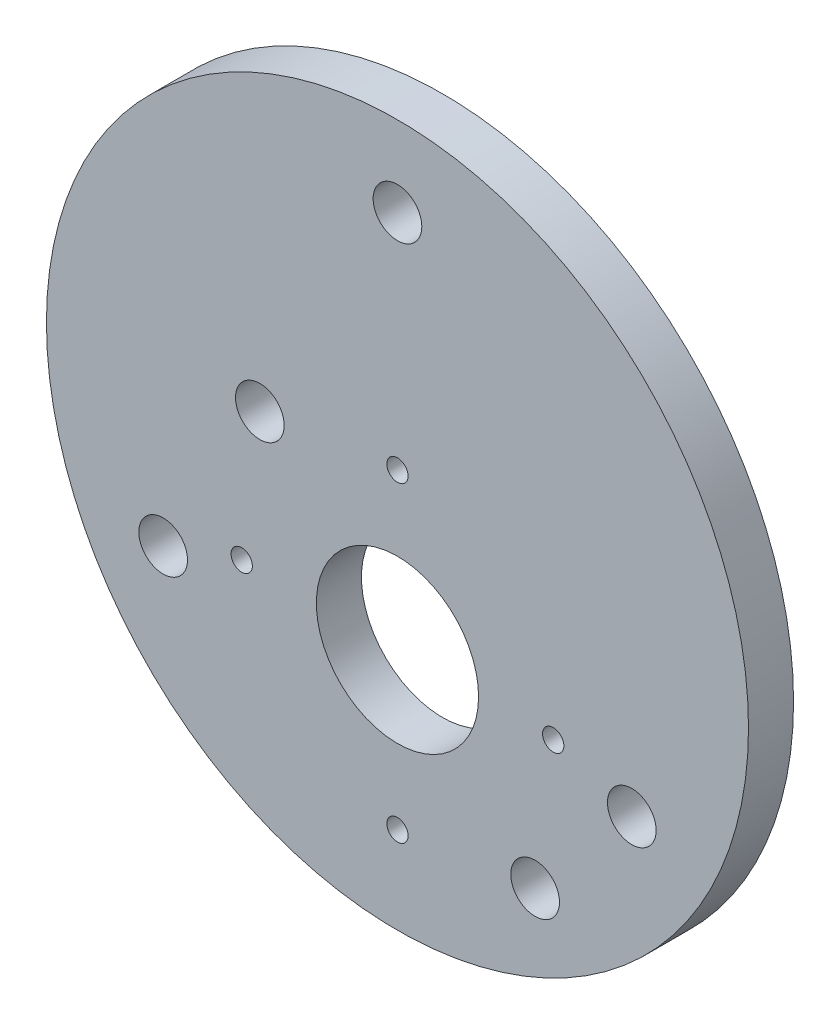
SolidWorks part; units mm, degrees
ref_plane "Front Plane" through (0, 0, 0) normal (0, 0, 1) x (1, 0, 0)
ref_plane "Top Plane" through (0, 0, 0) normal (0, 1, 0) x (1, 0, 0)
ref_plane "Right Plane" through (0, 0, 0) normal (1, 0, 0) x (0, 0, -1)
sketch "Sketch1" plane through (0, 0, 0) normal (0, 0, 1) x (1, 0, 0)
  circle A0 centre (0, 0) radius 49.4665
  dimension "D1" = 98.933
extrude "Boss-Extrude1" add sketch "Sketch1" along normal blind 6.35
sketch "Sketch2" plane through (0, 0, 6.35) normal (0, 0, 1) x (1, 0, 0)
  line L0 (0, -37.1877) -> (0, 6.7077) construction
  line L1 (-21.9477, -15.24) -> (0, 6.7077)
  line L2 (-21.9477, -15.24) -> (0, -37.1877)
  line L3 (0, -37.1877) -> (21.9477, -15.24)
  line L4 (0, 6.7077) -> (21.9477, -15.24)
  line L5 (0, -15.24) -> (12.0918, -15.24) construction
  point P4 (0, -15.24)
  dimension "D1" = 31.0388
  dimension "D2" = 31.0388
  dimension "D3" = 15.24
  dimension "D4" = 90
hole_wizard "M3 Screw Hole - Ø3.0mm Dowel Hole" positions "Sketch3" profile "Sketch4" hole size "Ø3.0" standard "ANSI Metric" end condition through all
sketch "Sketch3" plane through (0, 0, 6.35) normal (0, 0, 1) x (1, 0, 0)
  point P0 (0, 6.7077)
  point P3 (-21.9477, -15.24)
  point P6 (0, -37.1877)
  point P9 (21.9477, -15.24)
sketch "Sketch4" plane through (0, 6.7077, 6.35) normal (1, 0, 0) x (0, -1, 0)
  line L0 (0, 0) -> (0, 6.35)
  line L1 (0, 6.35) -> (1.5, 6.35)
  line L2 (1.5, 6.35) -> (1.5, 0)
  line L5 (1.5, 0) -> (0, 0)
  line L11 (0, -6.35) -> (0, 107.95) construction
  dimension "Thru Hole Dia." = 3
  dimension "Thru Hole Depth" = 6.35
sketch "Sketch5" plane through (0, 0, 6.35) normal (0, 0, 1) x (1, 0, 0)
  line L0 (0, -37.1877) -> (0, 6.7077) construction
  line L1 (-29.9941, -15.24) -> (0, 14.7541)
  line L2 (-29.9941, -15.24) -> (0, -45.2341)
  line L3 (0, -45.2341) -> (29.9941, -15.24)
  line L4 (0, 14.7541) -> (29.9941, -15.24)
  line L5 (-29.9941, -15.24) -> (29.9941, -15.24) construction
  line L6 (0, -45.2341) -> (0, 14.7541) construction
  line L7 (-19.3974, 4.1574) -> (0, -15.24) construction
  line L8 (0, -15.24) -> (32.8719, -15.24) construction
  line L9 (0, -15.24) -> (19.3974, -34.6374) construction
  circle A0 centre (19.3974, -34.6374) radius 3.429
  circle A1 centre (-19.3974, 4.1574) radius 3.429
  point P0 (0, -15.24)
  point P7 (0, -15.24)
  dimension "D3" = 6.858
  dimension "D5" = 6.858
  dimension "D1" = 42.418
  dimension "D4" = 42.418
  dimension "D6" = 27.432
  dimension "D7" = 135
extrude "Cut-Extrude1" cut sketch "Sketch5" against normal through all contours A0 | A1 region at (19.3974, -34.6374, 6.35)
sketch "Sketch6" plane through (0, 0, 6.35) normal (0, 0, 1) x (1, 0, 0)
  line L0 (0, 38.1282) -> (-33.02, -19.0641) construction
  line L1 (-33.02, -19.0641) -> (33.02, -19.0641) construction
  line L2 (33.02, -19.0641) -> (0, 38.1282) construction
  line L3 (-33.02, -19.0641) -> (0, 0) construction
  line L4 (0, 0) -> (33.02, -19.0641) construction
  line L5 (0, 0) -> (0, 38.1282) construction
  circle A0 centre (0, 38.1282) radius 3.429
  circle A1 centre (-33.02, -19.0641) radius 3.429
  circle A2 centre (33.02, -19.0641) radius 3.429
  dimension "D1" = 6.858
  dimension "D2" = 66.04
  dimension "D3" = 60
  dimension "D4" = 60
extrude "Cut-Extrude2" cut sketch "Sketch6" against normal through all
sketch "Sketch7" plane through (0, 0, 6.35) normal (0, 0, 1) x (1, 0, 0)
  line L0 (0, -37.1877) -> (0, 6.7077) construction
  circle A0 centre (0, -15.24) radius 11.43
  point P4 (0, -15.24)
  dimension "D1" = 22.86
extrude "Cut-Extrude3" cut sketch "Sketch7" against normal through all
sketch "Possible Plate Hole Reference" plane through (0, 0, 6.35) normal (0, 0, 1) x (1, 0, 0)
  line L0 (47.781, 12.8029) -> (-47.781, -12.8029) construction
  line L1 (0, 0) -> (49.4665, 0) construction
  circle A0 centre (0, 0) radius 49.4665 construction
  circle A1 centre (0, 0) radius 4.9466 construction
  circle A2 centre (0, 0) radius 49.4665 construction
  point P7 (0, 0)
  dimension "D2" = 9.8933
  dimension "D3" = 98.933
  dimension "D1" = 15
equation "\"D2@Possible Plate Hole Reference\"=0.1*\"D3@Possible Plate Hole Reference\""
